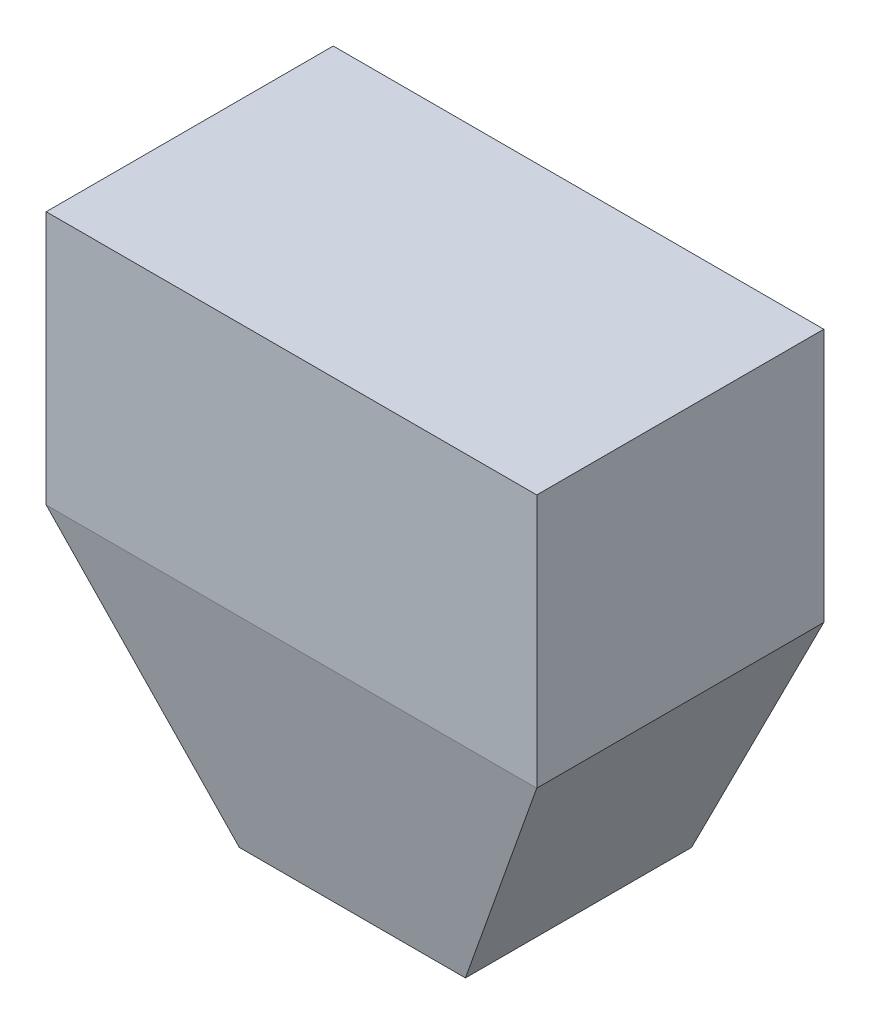
SolidWorks part; units mm, degrees
ref_plane "Front Plane" through (0, 0, 0) normal (0, 0, 1) x (1, 0, 0)
ref_plane "Top Plane" through (0, 0, 0) normal (0, 1, 0) x (1, 0, 0)
ref_plane "Right Plane" through (0, 0, 0) normal (1, 0, 0) x (0, 0, -1)
sketch "Sketch1" plane through (0, 0, 0) normal (0, 0, 1) x (1, 0, 0)
  line L0 (-10.1, 2.9) -> (-10.1, 9)
  line L1 (0, 0) -> (33.3867, 33.3867) construction
  line L2 (2.9, 10.1) -> (9, 10.1)
  line L3 (0, -29.7626) -> (0, 39.8721) construction
  line L4 (2.9, 10.1) -> (2.9, 7.9)
  line L5 (2.9, 7.9) -> (4.9, 7.9)
  line L6 (4.9, 7.9) -> (4.9, 5.749)
  line L7 (4.9, 5.749) -> (2.7515, 3.6005)
  line L8 (2.7515, 3.6005) -> (-2.7515, 3.6005)
  line L9 (3.6005, 2.7515) -> (3.6005, -2.7515)
  line L10 (5.749, 4.9) -> (3.6005, 2.7515)
  line L11 (7.9, 4.9) -> (5.749, 4.9)
  line L12 (7.9, 2.9) -> (7.9, 4.9)
  line L13 (10.1, 2.9) -> (7.9, 2.9)
  line L14 (10.1, 2.9) -> (10.1, 9)
  line L15 (-10.1, 2.9) -> (-7.9, 2.9)
  line L16 (-7.9, 2.9) -> (-7.9, 4.9)
  line L17 (-7.9, 4.9) -> (-5.749, 4.9)
  line L18 (-5.749, 4.9) -> (-3.6005, 2.7515)
  line L19 (-3.6005, 2.7515) -> (-3.6005, -2.7515)
  line L20 (-4.9, 5.749) -> (-2.7515, 3.6005)
  line L21 (-4.9, 7.9) -> (-4.9, 5.749)
  line L22 (-2.9, 7.9) -> (-4.9, 7.9)
  line L23 (-2.9, 10.1) -> (-2.9, 7.9)
  line L24 (-2.9, 10.1) -> (-9, 10.1)
  line L25 (-36.4561, 0) -> (36.8951, 0) construction
  line L26 (-2.9, -10.1) -> (-9, -10.1)
  line L27 (-2.9, -10.1) -> (-2.9, -7.9)
  line L28 (-2.9, -7.9) -> (-4.9, -7.9)
  line L29 (-4.9, -7.9) -> (-4.9, -5.749)
  line L30 (-4.9, -5.749) -> (-2.7515, -3.6005)
  line L31 (-5.749, -4.9) -> (-3.6005, -2.7515)
  line L32 (-7.9, -4.9) -> (-5.749, -4.9)
  line L33 (-7.9, -2.9) -> (-7.9, -4.9)
  line L34 (-10.1, -2.9) -> (-7.9, -2.9)
  line L35 (10.1, -2.9) -> (10.1, -9)
  line L36 (10.1, -2.9) -> (7.9, -2.9)
  line L37 (7.9, -2.9) -> (7.9, -4.9)
  line L38 (7.9, -4.9) -> (5.749, -4.9)
  line L39 (5.749, -4.9) -> (3.6005, -2.7515)
  line L40 (2.7515, -3.6005) -> (-2.7515, -3.6005)
  line L41 (4.9, -5.749) -> (2.7515, -3.6005)
  line L42 (4.9, -7.9) -> (4.9, -5.749)
  line L43 (2.9, -7.9) -> (4.9, -7.9)
  line L44 (2.9, -10.1) -> (2.9, -7.9)
  line L45 (2.9, -10.1) -> (9, -10.1)
  line L46 (-10.1, -2.9) -> (-10.1, -9)
  line L47 (-15.1, 14.6) -> (13.1, 14.6)
  line L48 (-15.1, 14.6) -> (-15.1, -14.6)
  line L49 (-15.1, -14.6) -> (13.1, -14.6)
  line L50 (13.1, 14.6) -> (13.1, -14.6)
  arc A0 (9, 10.1) -> (10.1, 9) centre (9, 9) cw
  arc A1 (-9, 10.1) -> (-10.1, 9) centre (-9, 9) ccw
  arc A2 (-9, -10.1) -> (-10.1, -9) centre (-9, -9) cw
  arc A3 (9, -10.1) -> (10.1, -9) centre (9, -9) ccw
  point P0 (0, 0)
  point P63 (0, 0)
  point P64 (0, 0)
  point P66 (0, 0)
  point P69 (0, 0)
  dimension "D3" = 1.1
  dimension "D1" = 45
  dimension "D2" = 20.2
  dimension "D4" = 6.1
  dimension "D5" = 2.2
  dimension "D6" = 2
  dimension "D7" = 2.151
  dimension "D8" = 5.503
  dimension "D9" = 4.5
  dimension "D10" = 4.5
  dimension "D11" = 5
  dimension "D12" = 3
extrude "Boss-Extrude1" add sketch "Sketch1" against normal blind 3 contours L50 L47 L48 L49 A3 L45 L44 L43 L42 L41 L40 L30 L29 L28 L27 L26 A2 L46 L34 L33 L32 L31 L19 L18 L17 L16 L15 L0 A1 L24 L23 L22 L21 L20 L8 L7 L6 L5 L4 L2 A0 L14 L13 L12 L11 L10 L9 L39 L38 L37 | L45 A3 L35 L36 L37 L38 L39 L9 L10 L11 L12 L13 L14 A0 L2 L4 L5 L6 L7 L8 L20 L21 L22 L23 L24 A1 L0 L15 L16 L17 L18 L19 L31 L32 L33 L34 L46 A2 L26 L27 L28 L29 L30 L40 L41 L42 L43 L44 region at (0, 0, 0) region at (-1, 14.1941, 0)
extrude "Boss-Extrude2" add sketch "Sketch1<3>" against normal blind 30 from surface contours L50 L47 L48 L49 A3 L45 L44 L43 L42 L41 L40 L30 L29 L28 L27 L26 A2 L46 L34 L33 L32 L31 L19 L18 L17 L16 L15 L0 A1 L24 L23 L22 L21 L20 L8 L7 L6 L5 L4 L2 A0 L14 L13 L12 L11 L10 L9 L39 L38 L37 region at (-1, 14.1941, 0) starting at face at (-1, 0, -3)
sketch "Sketch1<3>" plane through (0, 0, 0) normal (0, 0, 1) x (1, 0, 0) same geometry as "Sketch1"
mirror "Mirror1" about plane through (-15.1, 0, -3) normal (-1, 0, 0) of "Boss-Extrude2", "Boss-Extrude1"
ref_plane "Plane1" through (0, -44.6, 0) normal (0, -1, 0) x (-1, 0, 0)
sketch "Sketch3" plane through (0, -44.6, 0) normal (0, -1, 0) x (-1, 0, 0)
  line L0 (15.1, 33) -> (15.1, 0) construction
  line L1 (43.3, 33) -> (-13.1, 33) construction
  line L2 (43.3, 0) -> (-13.1, 0) construction
  line L4 (2.1, 7) -> (28.1, 7)
  line L5 (2.1, 7) -> (2.1, 33)
  line L6 (2.1, 33) -> (28.1, 33)
  line L7 (28.1, 7) -> (28.1, 33)
  line L8 (2.1, 7) -> (28.1, 33) construction
  line L9 (2.1, 33) -> (28.1, 7) construction
  line L10 (4.9, 9.8) -> (25.3, 9.8)
  line L11 (4.9, 9.8) -> (4.9, 30.2)
  line L12 (4.9, 30.2) -> (25.3, 30.2)
  line L13 (25.3, 9.8) -> (25.3, 30.2)
  line L14 (4.9, 9.8) -> (25.3, 30.2) construction
  line L15 (4.9, 30.2) -> (25.3, 9.8) construction
  point P6 (15.1, 20)
  point P11 (22.5, 11.0599)
  point P12 (15.1, 20)
  point P17 (25.3, 10.4387)
  dimension "D1" = 2.8
  dimension "D2" = 2.8
  dimension "D3" = 20.4
loft "Loft1" add section face at (-15.1, -14.6, -16.5) section "Sketch3"
extrude "Cut-Extrude1" cut sketch "Sketch3<3>" against normal blind 30 contours L10 L13 L12 L11 region at (-15.1, -44.6, -20)
sketch "Sketch3<3>" plane through (0, -44.6, 0) normal (0, -1, 0) x (-1, 0, 0) same geometry as "Sketch3"
sketch "Sketch4" plane through (0, 0, -33) normal (0, 0, -1) x (-1, 0, 0)
  line L0 (15.1, -44.6) -> (15.1, 14.6) construction
  line L1 (2.1, -44.6) -> (28.1, -44.6) construction
  line L2 (43.3, 14.6) -> (-13.1, 14.6) construction
  circle A0 centre (15.1, -37.1) radius 2
  circle A1 centre (15.1, -22.1) radius 2
  dimension "D3" = 4
  dimension "D1" = 7.5
  dimension "D2" = 15
extrude "Cut-Extrude2" cut sketch "Sketch4" against normal up to next
